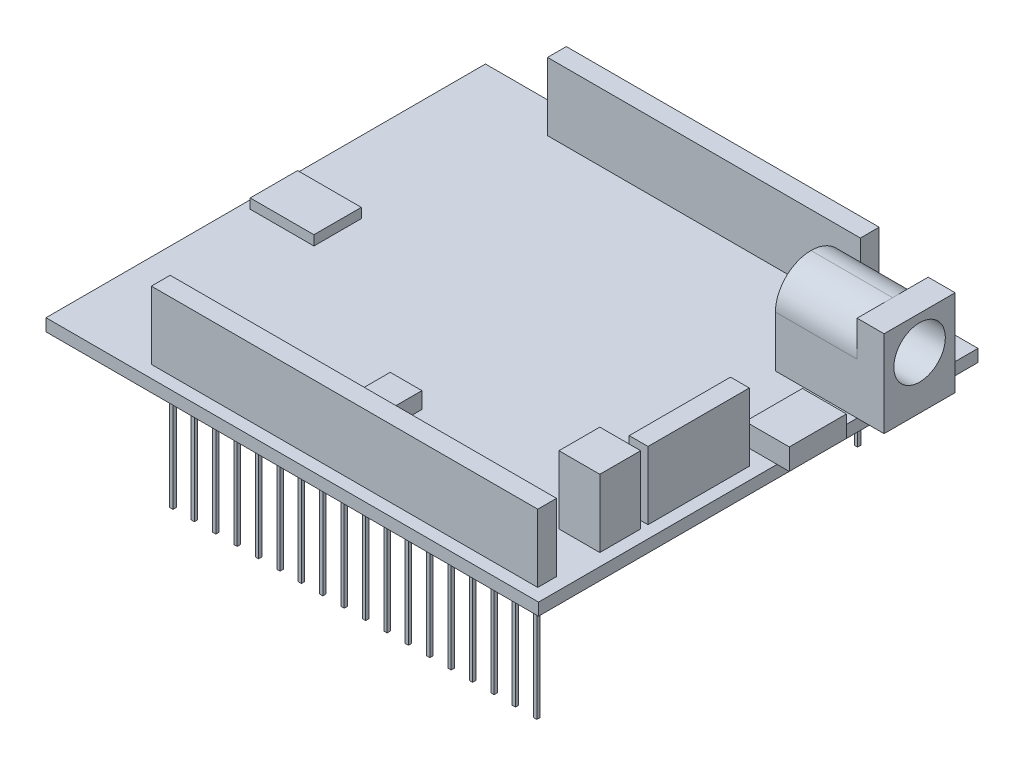
SolidWorks part; units mm, degrees
ref_plane "Front Plane" through (0, 0, 0) normal (0, 0, 1) x (1, 0, 0)
ref_plane "Top Plane" through (0, 0, 0) normal (0, 1, 0) x (1, 0, 0)
ref_plane "Right Plane" through (0, 0, 0) normal (1, 0, 0) x (0, 0, -1)
sketch "Sketch1" plane through (0, 0, 0) normal (0, 1, 0) x (1, 0, 0)
  line L1 (-30.15, 26.9) -> (30.15, 26.9)
  line L2 (-30.15, 26.9) -> (-30.15, -26.9)
  line L3 (-30.15, -26.9) -> (30.15, -26.9)
  line L4 (30.15, 26.9) -> (30.15, -26.9)
  line L5 (-30.15, 26.9) -> (30.15, -26.9) construction
  line L6 (-30.15, -26.9) -> (30.15, 26.9) construction
  point P0 (0, 0)
  dimension "D1" = 60.3
  dimension "D2" = 53.8
extrude "Boss-Extrude1" add sketch "Sketch1" along normal blind 1.5
sketch "Sketch2" plane through (0, 1.5, 0) normal (0, 1, 0) x (1, 0, 0)
  line L0 (-30.15, 26.9) -> (-30.15, -26.9) construction
  line L1 (-18.75, 25.4) -> (19.55, 25.4)
  line L2 (-18.75, 25.4) -> (-18.75, 23.1)
  line L3 (-18.75, 23.1) -> (19.55, 23.1)
  line L4 (19.55, 25.4) -> (19.55, 23.1)
  line L5 (-18.75, 25.4) -> (19.55, 23.1) construction
  line L6 (-18.75, 23.1) -> (19.55, 25.4) construction
  line L7 (30.15, 26.9) -> (-30.15, 26.9) construction
  line L8 (-30.15, -26.9) -> (30.15, -26.9) construction
  line L9 (-18.75, -23.1) -> (28.55, -23.1)
  line L10 (-18.75, -23.1) -> (-18.75, -25.4)
  line L11 (-18.75, -25.4) -> (28.55, -25.4)
  line L12 (28.55, -23.1) -> (28.55, -25.4)
  line L13 (-18.75, -23.1) -> (28.55, -25.4) construction
  line L14 (-18.75, -25.4) -> (28.55, -23.1) construction
  point P0 (0.4, 24.25)
  point P9 (4.9, -24.25)
  dimension "D1" = 38.3
  dimension "D2" = 2.3
  dimension "D3" = 11.4
  dimension "D4" = 1.5
  dimension "D5" = 2.3
  dimension "D6" = 47.3
  dimension "D7" = 1.5
extrude "Boss-Extrude2" add sketch "Sketch2" along normal blind 8.3
sketch "Sketch3" plane through (0, 1.5, 0) normal (0, 1, 0) x (1, 0, 0)
  line L0 (30.15, -26.9) -> (30.15, 26.9) construction
  line L1 (28.65, -17.9) -> (23.65, -17.9)
  line L2 (28.65, -17.9) -> (28.65, -12.9)
  line L3 (28.65, -12.9) -> (23.65, -12.9)
  line L4 (23.65, -17.9) -> (23.65, -12.9)
  line L5 (28.65, -17.9) -> (23.65, -12.9) construction
  line L6 (28.65, -12.9) -> (23.65, -17.9) construction
  line L7 (-18.75, -25.4) -> (28.55, -25.4) construction
  point P0 (26.15, -15.4)
  dimension "D1" = 5
  dimension "D2" = 5
  dimension "D3" = 1.5
  dimension "D4" = 12.5
extrude "Boss-Extrude3" add sketch "Sketch3" along normal up to surface (8.3 mm away) up to face at (4.9, 9.8, 24.25)
sketch "Sketch4" plane through (0, 1.5, 0) normal (0, 1, 0) x (1, 0, 0)
  line L0 (-18.75, -25.4) -> (28.55, -25.4) construction
  line L1 (28.65, 0.4) -> (26.35, 0.4)
  line L2 (28.65, 0.4) -> (28.65, -12)
  line L3 (28.65, -12) -> (26.35, -12)
  line L4 (26.35, 0.4) -> (26.35, -12)
  line L5 (28.65, 0.4) -> (26.35, -12) construction
  line L6 (28.65, -12) -> (26.35, 0.4) construction
  line L7 (30.15, -26.9) -> (30.15, 26.9) construction
  point P0 (27.5, -5.8)
  dimension "D1" = 12.4
  dimension "D2" = 25.8
  dimension "D3" = 2.3
  dimension "D4" = 1.5
extrude "Boss-Extrude4" add sketch "Sketch4" along normal up to surface (8.3 mm away) up to face at (4.9, 9.8, 24.25)
sketch "Sketch5" plane through (0, 1.5, 0) normal (0, 1, 0) x (1, 0, 0)
  line L0 (-18.75, -25.4) -> (28.55, -25.4) construction
  line L1 (26.25, 9.3) -> (31.65, 9.3)
  line L2 (26.25, 9.3) -> (26.25, 2.3)
  line L3 (26.25, 2.3) -> (31.65, 2.3)
  line L4 (31.65, 9.3) -> (31.65, 2.3)
  line L5 (26.25, 9.3) -> (31.65, 2.3) construction
  line L6 (26.25, 2.3) -> (31.65, 9.3) construction
  line L7 (30.15, -26.9) -> (30.15, 26.9) construction
  point P0 (28.95, 5.8)
  dimension "D1" = 7
  dimension "D2" = 34.7
  dimension "D3" = 1.5
  dimension "D4" = 5.4
extrude "Boss-Extrude5" add sketch "Sketch5" along normal blind 2.6
sketch "Sketch6" plane through (0, 1.5, 0) normal (0, 1, 0) x (1, 0, 0)
  line L0 (-30.15, 26.9) -> (-30.15, -26.9) construction
  line L1 (-29.15, 2.9) -> (-21.35, 2.9)
  line L2 (-29.15, 2.9) -> (-29.15, -2.9)
  line L3 (-29.15, -2.9) -> (-21.35, -2.9)
  line L4 (-21.35, 2.9) -> (-21.35, -2.9)
  line L5 (-29.15, 2.9) -> (-21.35, -2.9) construction
  line L6 (-29.15, -2.9) -> (-21.35, 2.9) construction
  point P0 (-25.25, 0)
  dimension "D1" = 7.8
  dimension "D2" = 5.8
  dimension "D3" = 1
extrude "Boss-Extrude6" add sketch "Sketch6" along normal blind 1.2
sketch "Sketch7" plane through (0, 1.5, 0) normal (0, 1, 0) x (1, 0, 0)
  line L0 (30.15, 26.9) -> (-30.15, 26.9) construction
  line L1 (20.15, 20.8) -> (30.15, 20.8)
  line L2 (20.15, 20.8) -> (20.15, 12.1)
  line L3 (20.15, 12.1) -> (30.15, 12.1)
  line L4 (30.15, 20.8) -> (30.15, 12.1)
  line L5 (20.15, 20.8) -> (30.15, 12.1) construction
  line L6 (20.15, 12.1) -> (30.15, 20.8) construction
  line L7 (30.15, 9.3) -> (30.15, 26.9) construction
  point P0 (25.15, 16.45)
  dimension "D1" = 10
  dimension "D2" = 8.7
  dimension "D3" = 14.8
extrude "Boss-Extrude7" add sketch "Sketch7" along normal blind 10.6
fillet "Fillet1" radius 4.35 2 edges at (25.15, 12.1, -20.8) (25.15, 12.1, -12.1)
sketch "Sketch9" plane through (0, 1.5, 0) normal (0, 1, 0) x (1, 0, 0)
  line L0 (20.15, 16.45) -> (30.15, 16.45) construction
  line L1 (33.45, 20.8) -> (30.15, 20.8)
  line L2 (33.45, 20.8) -> (33.45, 12.1)
  line L3 (33.45, 12.1) -> (30.15, 12.1)
  line L4 (30.15, 20.8) -> (30.15, 12.1)
  line L5 (33.45, 20.8) -> (30.15, 12.1) construction
  line L6 (33.45, 12.1) -> (30.15, 20.8) construction
  line L7 (30.15, 9.3) -> (30.15, 12.1) construction
  line L8 (30.15, 20.8) -> (20.15, 20.8) construction
  point P0 (31.8, 16.45)
  dimension "D1" = 3.3
extrude "Boss-Extrude8" add sketch "Sketch9" along normal up to vertex (10.6 mm away) up to point (30.15, 12.1, -16.45)
sketch "Sketch10" plane through (33.45, 0, 0) normal (1, 0, 0) x (0, 0, -1)
  line L0 (12.1, 12.1) -> (20.8, 12.1) construction
  circle A0 centre (16.45, 7.95) radius 3.15
  dimension "D1" = 6.3
  dimension "D2" = 4.15
extrude "Cut-Extrude1" cut sketch "Sketch10" against normal blind 10.6
sketch "Sketch11" plane through (0, 9.8, 0) normal (0, 1, 0) x (1, 0, 0)
  line L1 (-17.45, 24.45) -> (-17.05, 24.45)
  line L2 (-17.45, 24.45) -> (-17.45, 24.05)
  line L3 (-17.45, 24.05) -> (-17.05, 24.05)
  line L4 (-17.05, 24.45) -> (-17.05, 24.05)
  line L5 (-17.45, 24.45) -> (-17.05, 24.05) construction
  line L6 (-17.45, 24.05) -> (-17.05, 24.45) construction
  line L7 (-18.75, 25.4) -> (-18.75, 23.1) construction
  line L8 (-14.7346, 24.45) -> (-14.7346, 24.05)
  line L9 (-14.7346, 24.45) -> (-14.3346, 24.45)
  line L10 (-14.3346, 24.45) -> (-14.3346, 24.05)
  line L11 (-14.7346, 24.05) -> (-14.3346, 24.05)
  line L12 (-12.0192, 24.45) -> (-12.0192, 24.05)
  line L13 (-12.0192, 24.45) -> (-11.6192, 24.45)
  line L14 (-11.6192, 24.45) -> (-11.6192, 24.05)
  line L15 (-12.0192, 24.05) -> (-11.6192, 24.05)
  line L16 (-9.3039, 24.45) -> (-9.3039, 24.05)
  line L17 (-9.3039, 24.45) -> (-8.9039, 24.45)
  line L18 (-8.9039, 24.45) -> (-8.9039, 24.05)
  line L19 (-9.3039, 24.05) -> (-8.9039, 24.05)
  line L20 (-6.5885, 24.45) -> (-6.5885, 24.05)
  line L21 (-6.5885, 24.45) -> (-6.1885, 24.45)
  line L22 (-6.1885, 24.45) -> (-6.1885, 24.05)
  line L23 (-6.5885, 24.05) -> (-6.1885, 24.05)
  line L24 (-3.8731, 24.45) -> (-3.8731, 24.05)
  line L25 (-3.8731, 24.45) -> (-3.4731, 24.45)
  line L26 (-3.4731, 24.45) -> (-3.4731, 24.05)
  line L27 (-3.8731, 24.05) -> (-3.4731, 24.05)
  line L28 (-1.1577, 24.45) -> (-1.1577, 24.05)
  line L29 (-1.1577, 24.45) -> (-0.7577, 24.45)
  line L30 (-0.7577, 24.45) -> (-0.7577, 24.05)
  line L31 (-1.1577, 24.05) -> (-0.7577, 24.05)
  line L32 (1.5577, 24.45) -> (1.5577, 24.05)
  line L33 (1.5577, 24.45) -> (1.9577, 24.45)
  line L34 (1.9577, 24.45) -> (1.9577, 24.05)
  line L35 (1.5577, 24.05) -> (1.9577, 24.05)
  line L36 (4.273, 24.45) -> (4.273, 24.05)
  line L37 (4.273, 24.45) -> (4.673, 24.45)
  line L38 (4.673, 24.45) -> (4.673, 24.05)
  line L39 (4.273, 24.05) -> (4.673, 24.05)
  line L40 (6.9884, 24.45) -> (6.9884, 24.05)
  line L41 (6.9884, 24.45) -> (7.3884, 24.45)
  line L42 (7.3884, 24.45) -> (7.3884, 24.05)
  line L43 (6.9884, 24.05) -> (7.3884, 24.05)
  line L44 (9.7038, 24.45) -> (9.7038, 24.05)
  line L45 (9.7038, 24.45) -> (10.1038, 24.45)
  line L46 (10.1038, 24.45) -> (10.1038, 24.05)
  line L47 (9.7038, 24.05) -> (10.1038, 24.05)
  line L48 (12.4192, 24.45) -> (12.4192, 24.05)
  line L49 (12.4192, 24.45) -> (12.8192, 24.45)
  line L50 (12.8192, 24.45) -> (12.8192, 24.05)
  line L51 (12.4192, 24.05) -> (12.8192, 24.05)
  line L52 (15.1346, 24.45) -> (15.1346, 24.05)
  line L53 (15.1346, 24.45) -> (15.5346, 24.45)
  line L54 (15.5346, 24.45) -> (15.5346, 24.05)
  line L55 (15.1346, 24.05) -> (15.5346, 24.05)
  line L56 (17.8499, 24.45) -> (17.8499, 24.05)
  line L57 (17.8499, 24.45) -> (18.2499, 24.45)
  line L58 (18.2499, 24.45) -> (18.2499, 24.05)
  line L59 (17.8499, 24.05) -> (18.2499, 24.05)
  point P0 (-17.25, 24.25)
  point P8 (-18.75, 24.25)
  dimension "D1" = 0.4
  dimension "D2" = 0.4
  dimension "D3" = 1.5
  dimension "D4" = 14
extrude "Boss-Extrude9" add sketch "Sketch11" against normal blind 23.3
sketch "Sketch12" plane through (0, 9.8, 0) normal (0, 1, 0) x (1, 0, 0)
  line L1 (-18.75, -23.1) -> (-18.75, -25.4) construction
  line L2 (-17.45, -24.05) -> (-17.05, -24.05)
  line L3 (-17.45, -24.05) -> (-17.45, -24.45)
  line L4 (-17.45, -24.45) -> (-17.05, -24.45)
  line L5 (-17.05, -24.05) -> (-17.05, -24.45)
  line L6 (-17.45, -24.05) -> (-17.05, -24.45) construction
  line L7 (-17.45, -24.45) -> (-17.05, -24.05) construction
  line L8 (-14.83, -24.05) -> (-14.83, -24.45)
  line L9 (-14.83, -24.05) -> (-14.43, -24.05)
  line L10 (-14.43, -24.05) -> (-14.43, -24.45)
  line L11 (-14.83, -24.45) -> (-14.43, -24.45)
  line L12 (-12.21, -24.05) -> (-12.21, -24.45)
  line L13 (-12.21, -24.05) -> (-11.81, -24.05)
  line L14 (-11.81, -24.05) -> (-11.81, -24.45)
  line L15 (-12.21, -24.45) -> (-11.81, -24.45)
  line L16 (-9.59, -24.05) -> (-9.59, -24.45)
  line L17 (-9.59, -24.05) -> (-9.19, -24.05)
  line L18 (-9.19, -24.05) -> (-9.19, -24.45)
  line L19 (-9.59, -24.45) -> (-9.19, -24.45)
  line L20 (-6.97, -24.05) -> (-6.97, -24.45)
  line L21 (-6.97, -24.05) -> (-6.57, -24.05)
  line L22 (-6.57, -24.05) -> (-6.57, -24.45)
  line L23 (-6.97, -24.45) -> (-6.57, -24.45)
  line L24 (-4.35, -24.05) -> (-4.35, -24.45)
  line L25 (-4.35, -24.05) -> (-3.95, -24.05)
  line L26 (-3.95, -24.05) -> (-3.95, -24.45)
  line L27 (-4.35, -24.45) -> (-3.95, -24.45)
  line L28 (-1.73, -24.05) -> (-1.73, -24.45)
  line L29 (-1.73, -24.05) -> (-1.33, -24.05)
  line L30 (-1.33, -24.05) -> (-1.33, -24.45)
  line L31 (-1.73, -24.45) -> (-1.33, -24.45)
  line L32 (0.89, -24.05) -> (0.89, -24.45)
  line L33 (0.89, -24.05) -> (1.29, -24.05)
  line L34 (1.29, -24.05) -> (1.29, -24.45)
  line L35 (0.89, -24.45) -> (1.29, -24.45)
  line L36 (3.51, -24.05) -> (3.51, -24.45)
  line L37 (3.51, -24.05) -> (3.91, -24.05)
  line L38 (3.91, -24.05) -> (3.91, -24.45)
  line L39 (3.51, -24.45) -> (3.91, -24.45)
  line L40 (6.13, -24.05) -> (6.13, -24.45)
  line L41 (6.13, -24.05) -> (6.53, -24.05)
  line L42 (6.53, -24.05) -> (6.53, -24.45)
  line L43 (6.13, -24.45) -> (6.53, -24.45)
  line L44 (8.75, -24.05) -> (8.75, -24.45)
  line L45 (8.75, -24.05) -> (9.15, -24.05)
  line L46 (9.15, -24.05) -> (9.15, -24.45)
  line L47 (8.75, -24.45) -> (9.15, -24.45)
  line L48 (11.37, -24.05) -> (11.37, -24.45)
  line L49 (11.37, -24.05) -> (11.77, -24.05)
  line L50 (11.77, -24.05) -> (11.77, -24.45)
  line L51 (11.37, -24.45) -> (11.77, -24.45)
  line L52 (13.99, -24.05) -> (13.99, -24.45)
  line L53 (13.99, -24.05) -> (14.39, -24.05)
  line L54 (14.39, -24.05) -> (14.39, -24.45)
  line L55 (13.99, -24.45) -> (14.39, -24.45)
  line L56 (16.61, -24.05) -> (16.61, -24.45)
  line L57 (16.61, -24.05) -> (17.01, -24.05)
  line L58 (17.01, -24.05) -> (17.01, -24.45)
  line L59 (16.61, -24.45) -> (17.01, -24.45)
  line L60 (19.23, -24.05) -> (19.23, -24.45)
  line L61 (19.23, -24.05) -> (19.63, -24.05)
  line L62 (19.63, -24.05) -> (19.63, -24.45)
  line L63 (19.23, -24.45) -> (19.63, -24.45)
  line L64 (21.85, -24.05) -> (21.85, -24.45)
  line L65 (21.85, -24.05) -> (22.25, -24.05)
  line L66 (22.25, -24.05) -> (22.25, -24.45)
  line L67 (21.85, -24.45) -> (22.25, -24.45)
  line L68 (24.47, -24.05) -> (24.47, -24.45)
  line L69 (24.47, -24.05) -> (24.87, -24.05)
  line L70 (24.87, -24.05) -> (24.87, -24.45)
  line L71 (24.47, -24.45) -> (24.87, -24.45)
  line L72 (27.09, -24.05) -> (27.09, -24.45)
  line L73 (27.09, -24.05) -> (27.49, -24.05)
  line L74 (27.49, -24.05) -> (27.49, -24.45)
  line L75 (27.09, -24.45) -> (27.49, -24.45)
  point P2 (-17.25, -24.25)
  point P8 (-18.75, -24.25)
  dimension "D1" = 0.4
  dimension "D2" = 0.4
  dimension "D3" = 1.5
  dimension "D4" = 18
extrude "Boss-Extrude10" add sketch "Sketch12" against normal up to surface (23.3 mm away) up to face at (-17.25, -13.5, -24.25)
sketch "Sketch13" plane through (0, 1.5, 0) normal (0, 1, 0) x (1, 0, 0)
  line L0 (30.15, -26.9) -> (30.15, 2.3) construction
  line L1 (-1.29, -13.62) -> (2.59, -13.62)
  line L2 (-1.29, -13.62) -> (-1.29, -18.78)
  line L3 (-1.29, -18.78) -> (2.59, -18.78)
  line L4 (2.59, -13.62) -> (2.59, -18.78)
  line L5 (-1.29, -13.62) -> (2.59, -18.78) construction
  line L6 (-1.29, -18.78) -> (2.59, -13.62) construction
  line L7 (-30.15, -26.9) -> (30.15, -26.9) construction
  point P0 (0.65, -16.2)
  dimension "D1" = 29.5
  dimension "D2" = 3.88
  dimension "D3" = 5.16
  dimension "D4" = 10.7
extrude "Boss-Extrude11" add sketch "Sketch13" along normal blind 2
sketch "Sketch14" plane through (0, 3.5, 0) normal (0, 1, 0) x (1, 0, 0)
  line L0 (-1.29, -13.62) -> (2.59, -18.78) construction
  line L1 (-1.29, -18.78) -> (2.59, -13.62) construction
  point P8 (0.65, -16.2)
